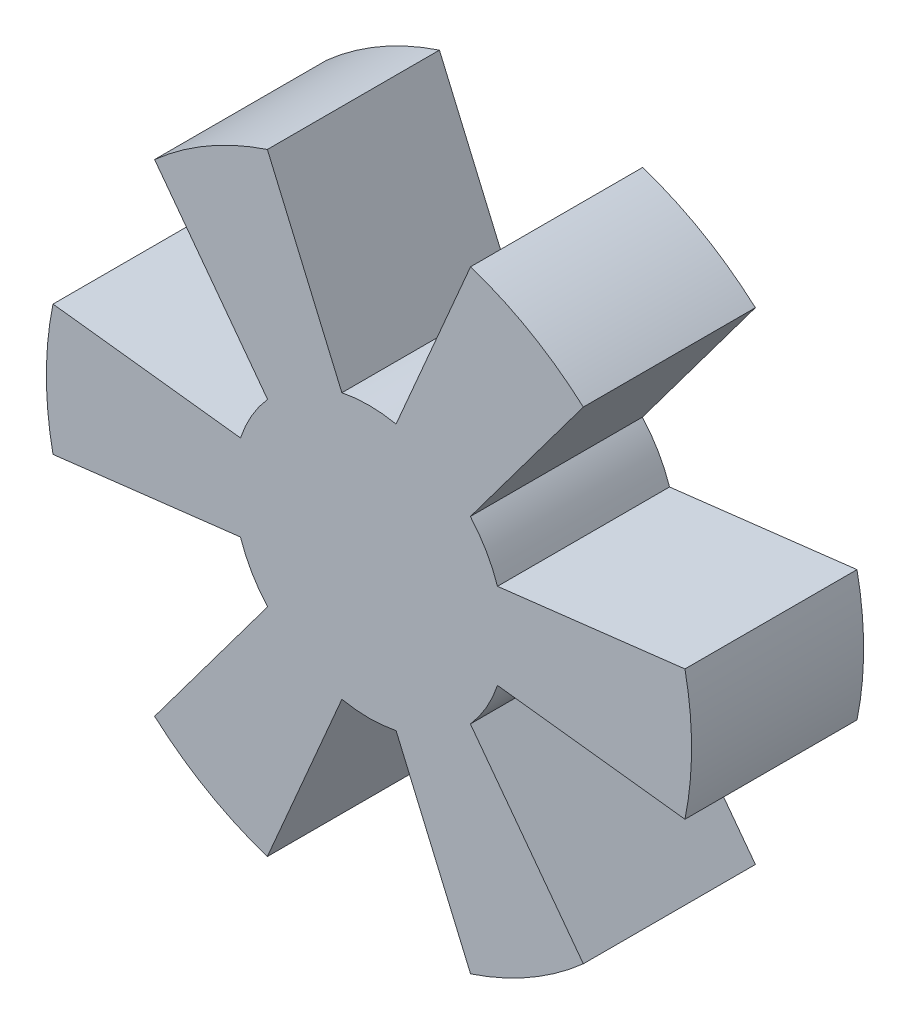
SolidWorks part; units mm, degrees
ref_plane "Płaszczyzna przednia" through (0, 0, 0) normal (0, 0, 1) x (1, 0, 0)
ref_plane "Płaszczyzna górna" through (0, 0, 0) normal (0, 1, 0) x (1, 0, 0)
ref_plane "Płaszczyzna prawa" through (0, 0, 0) normal (1, 0, 0) x (0, 0, -1)
sketch "Szkic1" plane through (0, 0, 0) normal (0, 0, 1) x (1, 0, 0)
  circle A0 centre (0, 0) radius 47.625
  circle A1 centre (0, 0) radius 20
  dimension "D1" = 95.25
  dimension "D2" = 40
extrude "Dodanie-wyciągnięcie1" add sketch "Szkic1" along normal blind 25.4
sketch "Szkic2" plane through (0, 0, 25.4) normal (0, 0, 1) x (1, 0, 0)
  line L0 (-4, -19.5959) -> (-15, -45.2011)
  line L1 (4, -19.5959) -> (15, -45.2011)
  circle A0 centre (0, 0) radius 20 construction
  circle A1 centre (0, 0) radius 47.625 construction
  arc A2 (-4, -19.5959) -> (4, -19.5959) centre (0, 0) ccw
  arc A3 (-15, -45.2011) -> (15, -45.2011) centre (0, 0) ccw
  dimension "D1" = 4
  dimension "D2" = 4
  dimension "D3" = 15
  dimension "D4" = 15
extrude "Wytnij-wyciągnięcie1" cut sketch "Szkic2" against normal up to next
sketch "Szkic3" plane through (0, 0, 25.4) normal (0, 0, 1) x (1, 0, 0)
  circle A0 centre (0, 0) radius 20
  arc A1 (4, -19.5959) -> (-4, -19.5959) centre (0, 0) ccw construction
extrude "Dodanie-wyciągnięcie2" add sketch "Szkic3" against normal blind 25.4
pattern_circular "Szyk kołowy1" count 6 over 360 about axis through (0, 0, 25.4) along (0, 0, 1) of "Wytnij-wyciągnięcie1"
